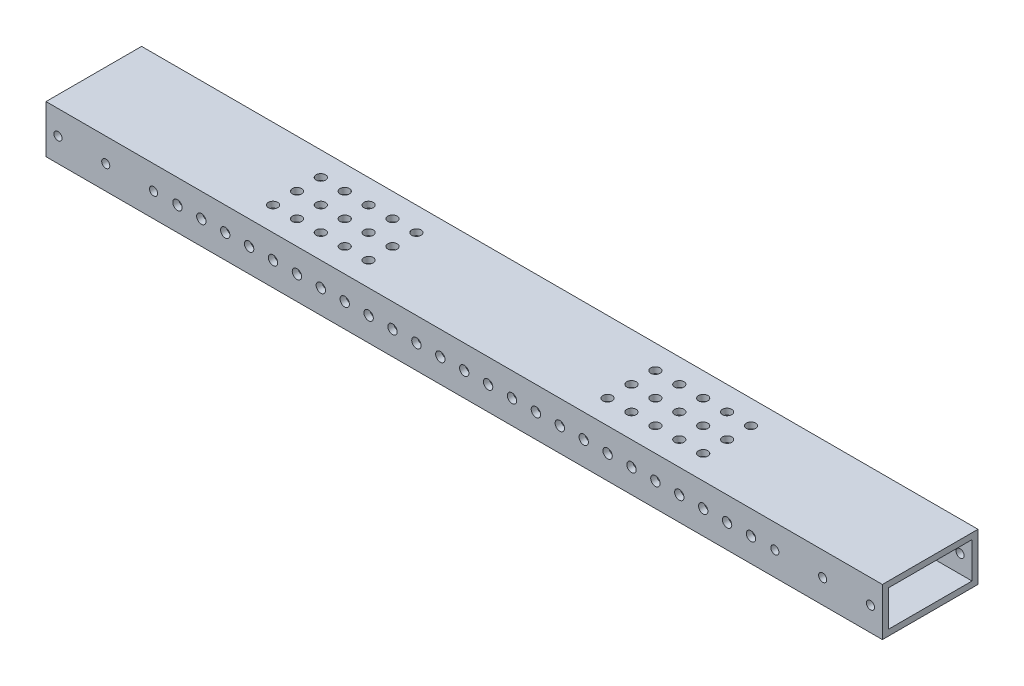
SolidWorks part; units mm, degrees
material "6061-T6 (SS)"
ref_plane "Front Plane" through (0, 0, 0) normal (0, 0, 1) x (1, 0, 0)
ref_plane "Top Plane" through (0, 0, 0) normal (0, 1, 0) x (1, 0, 0)
ref_plane "Right Plane" through (0, 0, 0) normal (1, 0, 0) x (0, 0, -1)
sketch "Sketch1" plane through (0, 0, 0) normal (1, 0, 0) x (0, 0, -1)
  line L1 (0, 0) -> (50.8, 0)
  line L2 (0, 0) -> (0, 25.4)
  line L3 (0, 25.4) -> (50.8, 25.4)
  line L4 (50.8, 0) -> (50.8, 25.4)
  dimension "D1" = 50.8
  dimension "D2" = 25.4
extrude "Boss-Extrude1" add sketch "Sketch1" along normal mid plane 444.5
shell "Shell1" thickness 3.175 removed face at (222.25, 12.7, -25.4) removed face at (-222.25, 12.7, -25.4)
sketch "Sketch2" plane through (0, 0, 0) normal (0, 0, 1) x (1, 0, 0)
  line L0 (-222.25, 25.4) -> (-222.25, 0) construction
  line L1 (222.25, 0) -> (-222.25, 0) construction
  circle A0 centre (-215.9, 12.7) radius 2.1527
  circle A1 centre (-190.5, 12.7) radius 2.1527
  circle A2 centre (-165.1, 12.7) radius 2.1527
  dimension "D1" = 4.3053
  dimension "D3" = 25.4
  dimension "D5" = 12.7
  dimension "D2" = 25.4
  dimension "D4" = 6.35
extrude "Cut-Extrude1" cut sketch "Sketch2" against normal through all
sketch "Sketch3" plane through (0, 0, 0) normal (0, 0, 1) x (1, 0, 0)
  line L0 (222.25, 25.4) -> (-222.25, 25.4) construction
  line L1 (-222.25, 25.4) -> (-222.25, 0) construction
  circle A0 centre (-152.4, 12.7) radius 2.4892
  dimension "D1" = 4.9784
  dimension "D2" = 12.7
  dimension "D3" = 69.85
extrude "Cut-Extrude2" cut sketch "Sketch3" against normal through all
mirror "Mirror1" about plane through (0, 0, 0) normal (1, 0, 0) of "Cut-Extrude1"
pattern_linear "LPattern1" count 25 spacing 12.7 along (1, 0, 0) of "Cut-Extrude2"
sketch "Sketch6" plane through (0, 0, 0) normal (0, -1, 0) x (1, 0, 0)
  circle A0 centre (63.5, -12.7) radius 2.4892 construction
  circle A1 centre (63.5, -25.4) radius 2.4892 construction
  circle A2 centre (76.2, -25.4) radius 2.4892 construction
  circle A3 centre (76.2, -12.7) radius 2.4892 construction
  circle A4 centre (88.9, -12.7) radius 2.4892 construction
  circle A5 centre (101.6, -25.4) radius 2.4892 construction
  circle A6 centre (88.9, -25.4) radius 2.4892 construction
  circle A7 centre (101.6, -12.7) radius 2.4892 construction
  circle A8 centre (114.3, -12.7) radius 2.4892 construction
  circle A9 centre (114.3, -25.4) radius 2.4892 construction
  circle A10 centre (114.3, -38.1) radius 2.4892 construction
  circle A11 centre (101.6, -38.1) radius 2.4892 construction
  circle A12 centre (88.9, -38.1) radius 2.4892 construction
  circle A13 centre (76.2, -38.1) radius 2.4892 construction
  circle A14 centre (63.5, -38.1) radius 2.4892 construction
  circle A15 centre (63.5, -12.7) radius 2.4892
  circle A16 centre (63.5, -25.4) radius 2.4892
  circle A17 centre (76.2, -25.4) radius 2.4892
  circle A18 centre (76.2, -12.7) radius 2.4892
  circle A19 centre (88.9, -12.7) radius 2.4892
  circle A20 centre (101.6, -25.4) radius 2.4892
  circle A21 centre (88.9, -25.4) radius 2.4892
  circle A22 centre (101.6, -12.7) radius 2.4892
  circle A23 centre (114.3, -12.7) radius 2.4892
  circle A24 centre (114.3, -25.4) radius 2.4892
  circle A25 centre (114.3, -38.1) radius 2.4892
  circle A26 centre (101.6, -38.1) radius 2.4892
  circle A27 centre (88.9, -38.1) radius 2.4892
  circle A28 centre (76.2, -38.1) radius 2.4892
  circle A29 centre (63.5, -38.1) radius 2.4892
  circle A30 centre (-114.3, -12.7) radius 2.4892 construction
  circle A31 centre (-101.6, -12.7) radius 2.4892 construction
  circle A32 centre (-88.9, -12.7) radius 2.4892 construction
  circle A33 centre (-76.2, -12.7) radius 2.4892 construction
  circle A34 centre (-63.5, -12.7) radius 2.4892 construction
  circle A35 centre (-63.5, -25.4) radius 2.4892 construction
  circle A36 centre (-76.2, -25.4) radius 2.4892 construction
  circle A37 centre (-88.9, -25.4) radius 2.4892 construction
  circle A38 centre (-101.6, -25.4) radius 2.4892 construction
  circle A39 centre (-114.3, -25.4) radius 2.4892 construction
  circle A40 centre (-114.3, -38.1) radius 2.4892 construction
  circle A41 centre (-101.6, -38.1) radius 2.4892 construction
  circle A42 centre (-88.9, -38.1) radius 2.4892 construction
  circle A43 centre (-76.2, -38.1) radius 2.4892 construction
  circle A44 centre (-63.5, -38.1) radius 2.4892 construction
  circle A45 centre (-114.3, -12.7) radius 2.4892
  circle A46 centre (-101.6, -12.7) radius 2.4892
  circle A47 centre (-88.9, -12.7) radius 2.4892
  circle A48 centre (-76.2, -12.7) radius 2.4892
  circle A49 centre (-63.5, -12.7) radius 2.4892
  circle A50 centre (-63.5, -25.4) radius 2.4892
  circle A51 centre (-76.2, -25.4) radius 2.4892
  circle A52 centre (-88.9, -25.4) radius 2.4892
  circle A53 centre (-101.6, -25.4) radius 2.4892
  circle A54 centre (-114.3, -25.4) radius 2.4892
  circle A55 centre (-114.3, -38.1) radius 2.4892
  circle A56 centre (-101.6, -38.1) radius 2.4892
  circle A57 centre (-88.9, -38.1) radius 2.4892
  circle A58 centre (-76.2, -38.1) radius 2.4892
  circle A59 centre (-63.5, -38.1) radius 2.4892
extrude "Cut-Extrude3" cut sketch "Sketch6" against normal through all
